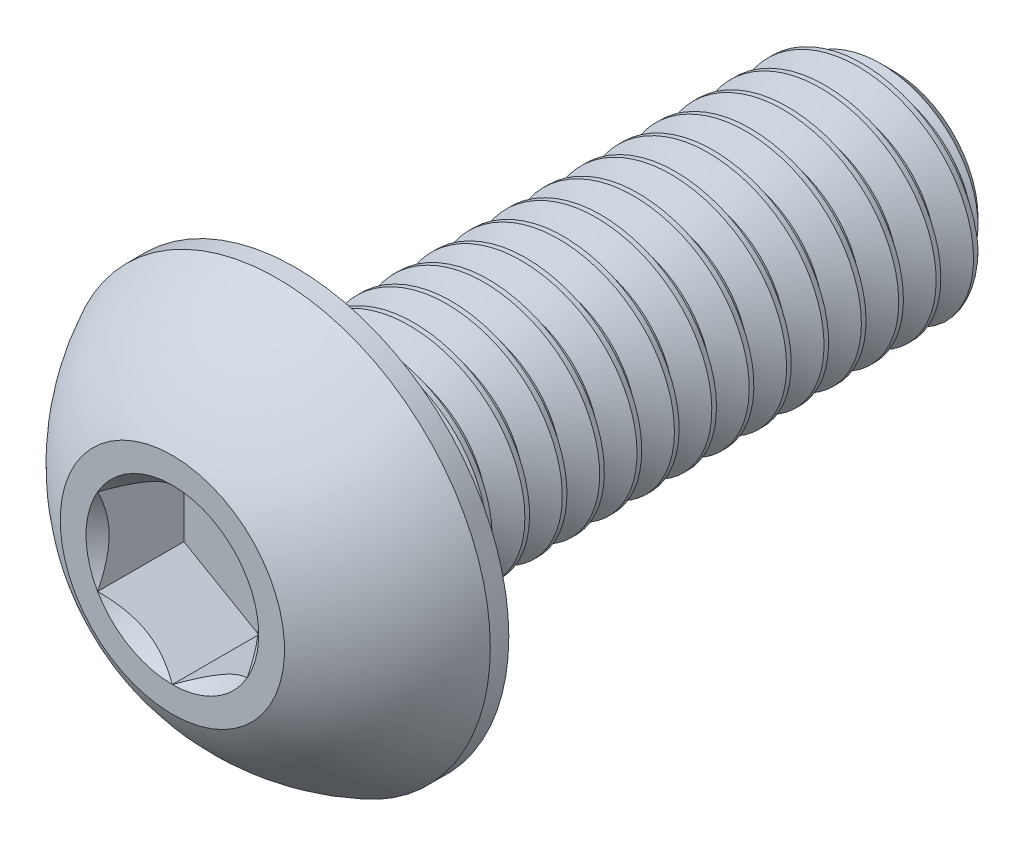
SolidWorks part; units mm, degrees
ref_plane "Front" through (0, 0, 0) normal (0, 0, 1) x (1, 0, 0)
ref_plane "Top" through (0, 0, 0) normal (0, 1, 0) x (1, 0, 0)
ref_plane "Right" through (0, 0, 0) normal (1, 0, 0) x (0, 0, -1)
sketch "Sketch1" plane through (0, 0, 0) normal (1, 0, 0) x (0, 0, -1)
  line L2 (1.65, 1.5) -> (9.65, 1.5)
  line L3 (9.65, 1.5) -> (9.65, 0)
  line L4 (9.65, 0) -> (1.65, 0)
  line L6 (1.4025, 2.85) -> (1.65, 2.85) construction
  line L7 (9.65, 1.5) -> (9.65, -1.5) construction
  line L8 (0, 0) -> (1.65, 0) construction
  line L9 (1.65, 2.85) -> (1.65, -2.85) construction
  line L11 (1.65, 1.5) -> (1.65, 0)
  line L13 (0, 1) -> (0, -1) construction
  line L14 (0, 1) -> (0, 1.5) construction
  arc A3 (0, 1.5) -> (1.4025, 2.85) centre (2.7948, 0) cw construction
  dimension "D1" = 0.2475
revolve "Revolve1" add sketch "Sketch1" angle 360 mid plane about L4
sketch "Sketch3" plane through (0, 0, -9.65) normal (0, 0, -1) x (-1, 0, 0)
  circle A0 centre (0, 0) radius 1.5
curve "Helix/Spiral1" pitch 0.5 height 8.5 radius 1.5 centre (0, 0, -9.65) axis (0, 0, 1) start towards (0, 1, 0)
sketch "Sketch2" plane through (0, 0, 0) normal (1, 0, 0) x (0, 0, -1)
  line L0 (9.65, 1.5) -> (10.0875, 1.5)
  line L1 (10.0875, 1.5) -> (9.9, 1.1752)
  line L2 (9.9, 1.1752) -> (9.8375, 1.1752)
  line L3 (9.8375, 1.1752) -> (9.65, 1.5)
  line L4 (9.7438, 1.3376) -> (9.9938, 1.3376) construction
  dimension "D1" = 60
  dimension "D2" = 0.0625
  dimension "D3" = 0.25
chamfer "Chamfer1" distance 0.375 angle 45 1 edges at (0, 1.5, -9.65)
sweep "Cut-Sweep1" cut profiles "Sketch2" path "Helix/Spiral1" align with end faces yes
sketch "Sketch7" plane through (0, 0, 0) normal (1, 0, 0) x (0, 0, -1)
  line L6 (1.4025, 2.85) -> (1.65, 2.85) construction
  line L8 (0, 0) -> (1.65, 0) construction
  line L11 (1.65, 2.85) -> (1.65, -2.85) construction
  line L12 (1.4025, 2.85) -> (1.65, 2.85)
  line L13 (0, 0) -> (1.65, 0)
  line L14 (0, 1) -> (0, -1) construction
  line L15 (1.65, 2.85) -> (1.65, 0)
  line L16 (0, 1.5) -> (0, 0)
  arc A2 (1.4025, 2.85) -> (0, 1.5) centre (2.7948, 0) ccw construction
  arc A3 (1.4025, 2.85) -> (0, 1.5) centre (2.7948, 0) ccw
revolve "Revolve2" add sketch "Sketch7" angle 360 mid plane about L13
sketch "Sketch5" plane through (0, 0, 0) normal (0, 0, 1) x (1, 0, 0)
  line L1 (1, -0.5774) -> (1, 0.5774)
  line L2 (1, 0.5774) -> (0, 1.1547)
  line L3 (0, 1.1547) -> (-1, 0.5774)
  line L4 (-1, 0.5774) -> (-1, -0.5774)
  line L5 (-1, -0.5774) -> (0, -1.1547)
  line L6 (0, -1.1547) -> (1, -0.5774)
  circle A0 centre (0, 0) radius 1 construction
extrude "Cut-Extrude2" cut sketch "Sketch5" against normal blind 1.155
sketch "Sketch6" plane through (0, 0, 0) normal (0, 0, 1) x (1, 0, 0)
  circle A0 centre (0, 0) radius 1.1547
extrude "Cut-Extrude3" cut sketch "Sketch6" against normal blind 1.155 draft 45
sketch "Sketch9" [suppressed] plane through (0, 0, -4.2164) normal (0, 0, 1) x (1, 0, 0)
  circle A2 centre (0, 0) radius 3.9687
extrude "Boss-Extrude2" [suppressed] add sketch "Sketch9" against normal offset from surface (9.525 mm away) 28.575 up to face at (0, 1.125, -9.65)
sketch "Sketch10" plane through (0, 0, 0) normal (1, 0, 0) x (0, 0, -1)
  line L0 (9.65, 1.5) -> (9.65, -1.5) construction
  point P0 (8.9, -1.5)
  dimension "D1" = 0.75
equation "\"D3@Helix/Spiral1\" = \"Lg@Sketch1\" + \"D4@Helix/Spiral1\""
equation "\"D2@Sketch2\" = \"D4@Helix/Spiral1\" * .125"
equation "\"D3@Sketch2\" = \"D4@Helix/Spiral1\" * .5"
equation "\"D1@Chamfer1\" = \"D4@Helix/Spiral1\" * .75"
equation "\"D1@Cut-Extrude2\" = \"Head Ht@Sketch1\" * .7"
equation "\"D1@Sketch1\" = \"Head Ht@Sketch1\" * .15"
equation "\"D1@Sketch10\" = \"D4@Helix/Spiral1\" * 1.5"
equation "\"D1@Cut-Extrude3\" = \"D1@Cut-Extrude2\""
